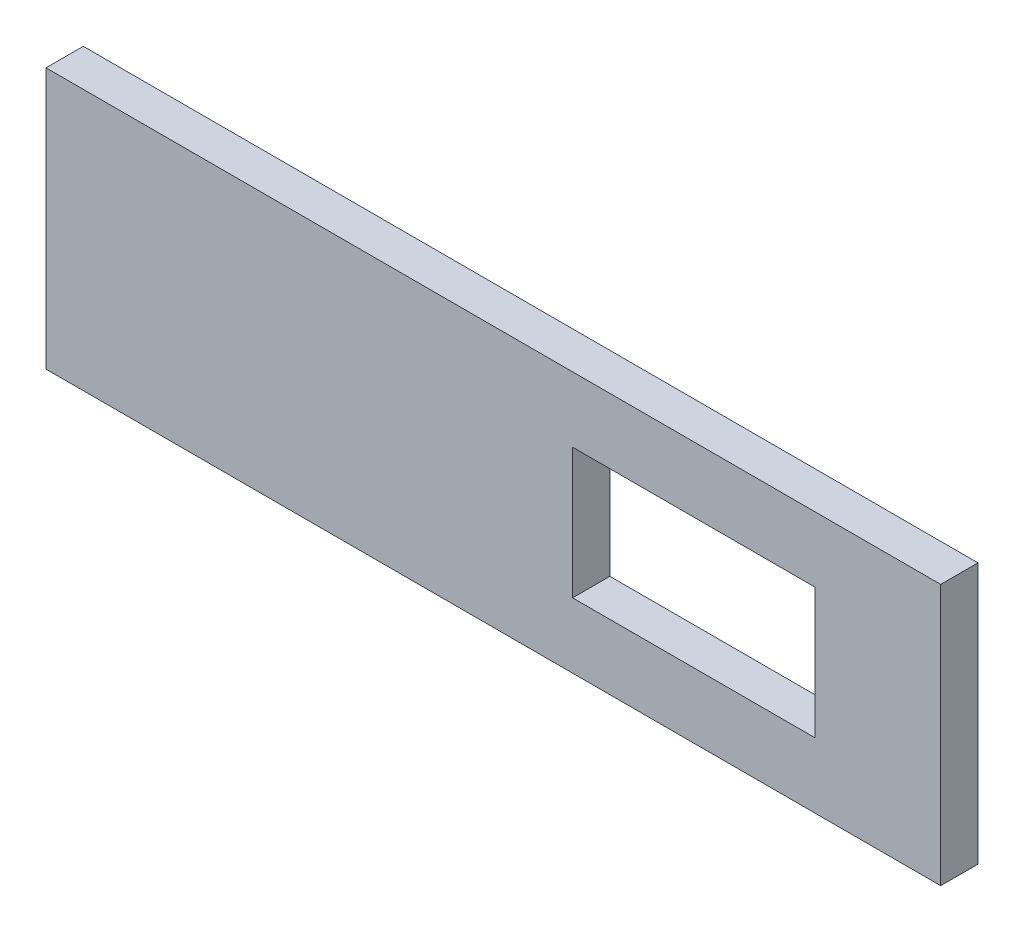
SolidWorks part; units mm, degrees
ref_plane "Front Plane" through (0, 0, 0) normal (0, 0, 1) x (1, 0, 0)
ref_plane "Top Plane" through (0, 0, 0) normal (0, 1, 0) x (1, 0, 0)
ref_plane "Right Plane" through (0, 0, 0) normal (1, 0, 0) x (0, 0, -1)
sketch "Sketch1" plane through (0, 0, 0) normal (0, 0, 1) x (1, 0, 0)
  line L0 (69.2576, 0) -> (-63.1151, 0) construction
  line L1 (42.067, 22.225) -> (-110.333, 22.225)
  line L2 (42.067, 22.225) -> (42.067, -22.225)
  line L3 (42.067, -22.225) -> (-110.333, -22.225)
  line L4 (-110.333, 22.225) -> (-110.333, -22.225)
  line L7 (25.98, 9.3599) -> (20.1295, 9.3599) construction
  line L8 (20.1295, -9.3599) -> (25.98, -9.3599) construction
  line L9 (-110.333, -69.85) -> (-110.333, 54.9538) construction
  line L10 (27.25, 6.27) -> (27.25, 8.0899) construction
  dimension "D1" = 44.45
  dimension "D2" = 14.817
extrude "Boss-Extrude1" add sketch "Sketch1" along normal blind 6.35
sketch "Sketch2" plane through (0, 0, 6.35) normal (0, 0, 1) x (1, 0, 0)
  line L0 (-43.1818, 0) -> (35.1848, 0) construction
  line L1 (-20.6375, 11.1125) -> (20.6375, 11.1125)
  line L2 (-20.6375, 11.1125) -> (-20.6375, -11.1125)
  line L3 (-20.6375, -11.1125) -> (20.6375, -11.1125)
  line L4 (20.6375, 11.1125) -> (20.6375, -11.1125)
  line L5 (-19.6295, 10.033) -> (19.6295, 10.033) construction
  line L6 (19.6295, -10.033) -> (-19.6295, -10.033) construction
  line L7 (0, 18.8234) -> (0, -13.1279) construction
  line L8 (-20.1295, -9.533) -> (-20.1295, 9.533) construction
  line L9 (20.1295, 9.533) -> (20.1295, -9.533) construction
  dimension "D1" = 22.225
  dimension "D2" = 41.275
extrude "Cut-Extrude1" cut sketch "Sketch2" against normal through all
